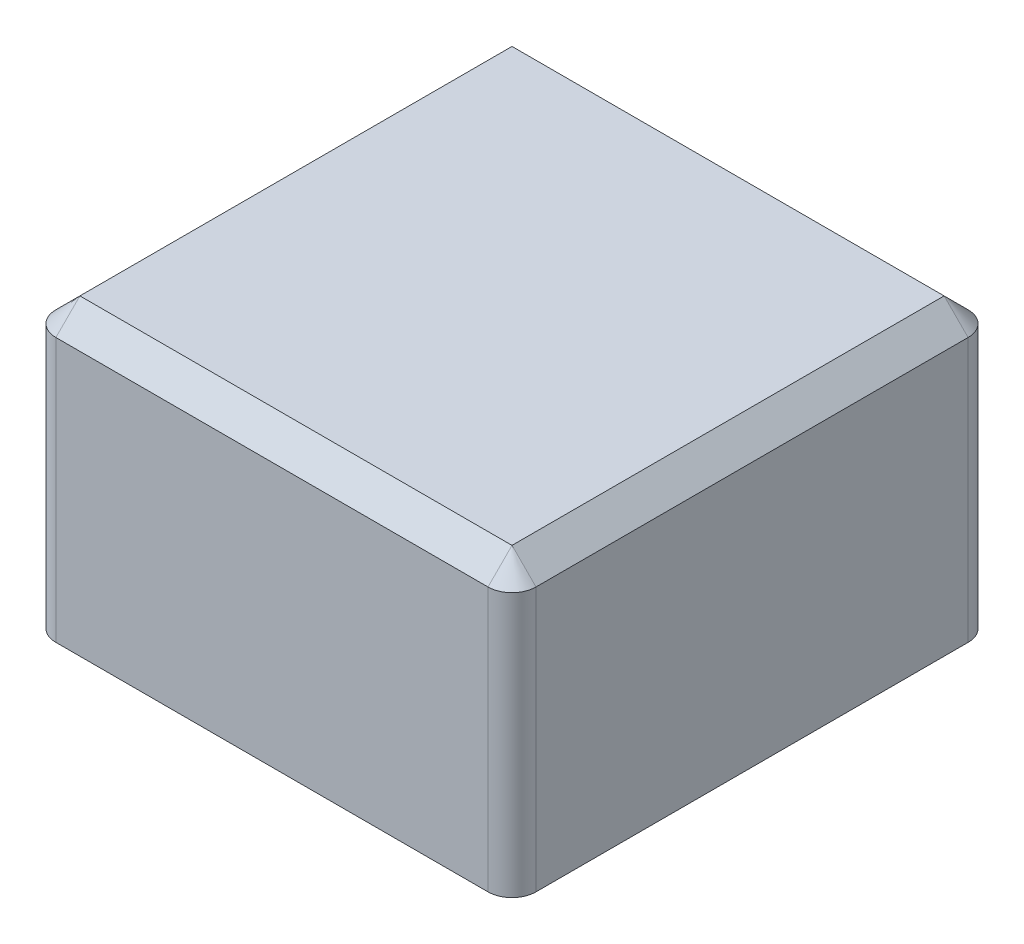
SolidWorks part; units mm, degrees
material "Beton"
ref_plane "Płaszczyzna przednia" through (0, 0, 0) normal (0, 0, 1) x (1, 0, 0)
ref_plane "Płaszczyzna górna" through (0, 0, 0) normal (0, 1, 0) x (1, 0, 0)
ref_plane "Płaszczyzna prawa" through (0, 0, 0) normal (1, 0, 0) x (0, 0, -1)
sketch3d "Szkic 3D1"
  line L0 (0, 0, 0) -> (100, 0, 0)
  line L1 (100, 0, 0) -> (100, 60, 0)
  line L2 (100, 60, 0) -> (0, 60, 0)
  line L3 (0, 60, 0) -> (0, 0, 0)
  dimension "D1" = 60
  dimension "D2" = 100
extrude "Dodanie-wyciągnięcie1" add sketch "Szkic 3D1" along direction (0, 0, 1) on the side of the normal blind 100 contours L0 L1 L2 L3
fillet "Zaokrąglenie3" radius 5 4 edges
chamfer "Sfazowanie1" distance 5 angle 45 8 edges at (98.5355, 60, 98.5355) (1.4645, 60, 98.5355) (1.4645, 60, 1.4645) (98.5355, 60, 1.4645)
